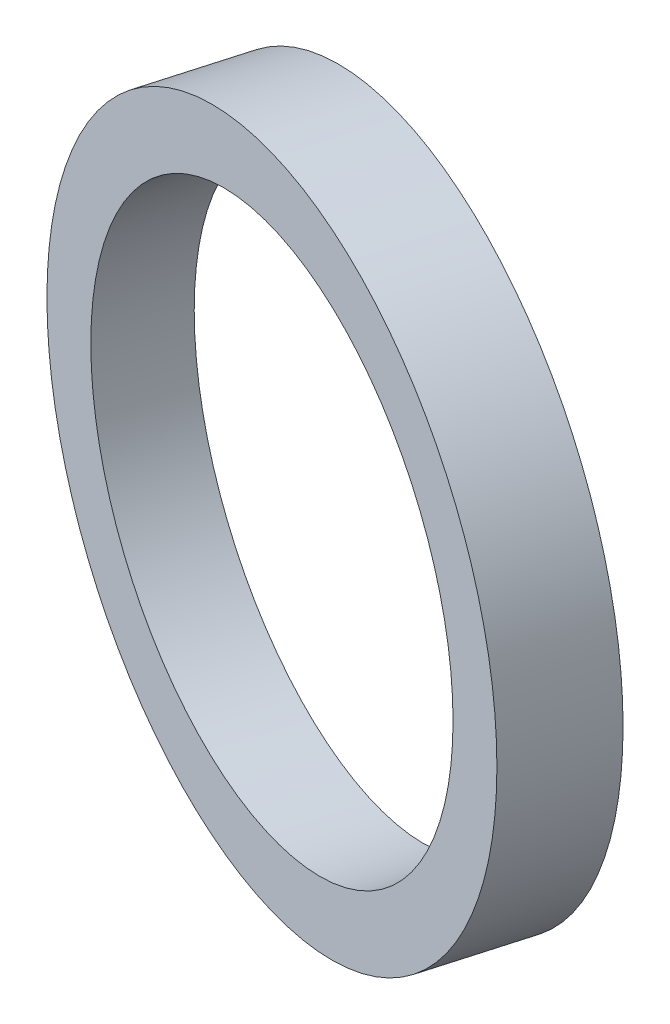
SolidWorks part; units mm, degrees
material "6061 Alloy"
ref_plane "Front Plane" through (0, 0, 0) normal (0, 0, 1) x (1, 0, 0)
ref_plane "Top Plane" through (0, 0, 0) normal (0, 1, 0) x (1, 0, 0)
ref_plane "Right Plane" through (0, 0, 0) normal (1, 0, 0) x (0, 0, -1)
sketch "Sketch3" plane through (0, 0, 0) normal (0, 1, 0) x (1, 0, 0)
  line L0 (2.855, -0.6343) -> (1.5694, -5.111)
  line L1 (1.5694, -5.111) -> (-1.2421, -4.3037)
  line L3 (-14.848, -7.936) -> (-8.8523, 12.9432) construction
  line L4 (2.855, -0.6343) -> (-0.1884, -0.6343)
  line L5 (-0.1884, -0.6343) -> (-1.2421, -4.3037)
  dimension "D1" = 2.9252
  dimension "D2" = 4.6576
  dimension "D3" = 3.8176
  dimension "D4" = 12.0748
ref_axis "Axis1" through (-14.848, 0, 7.936) along (0.276, 0, -0.9612)
revolve "Revolve3" add sketch "Sketch3" angle 360 about L3
